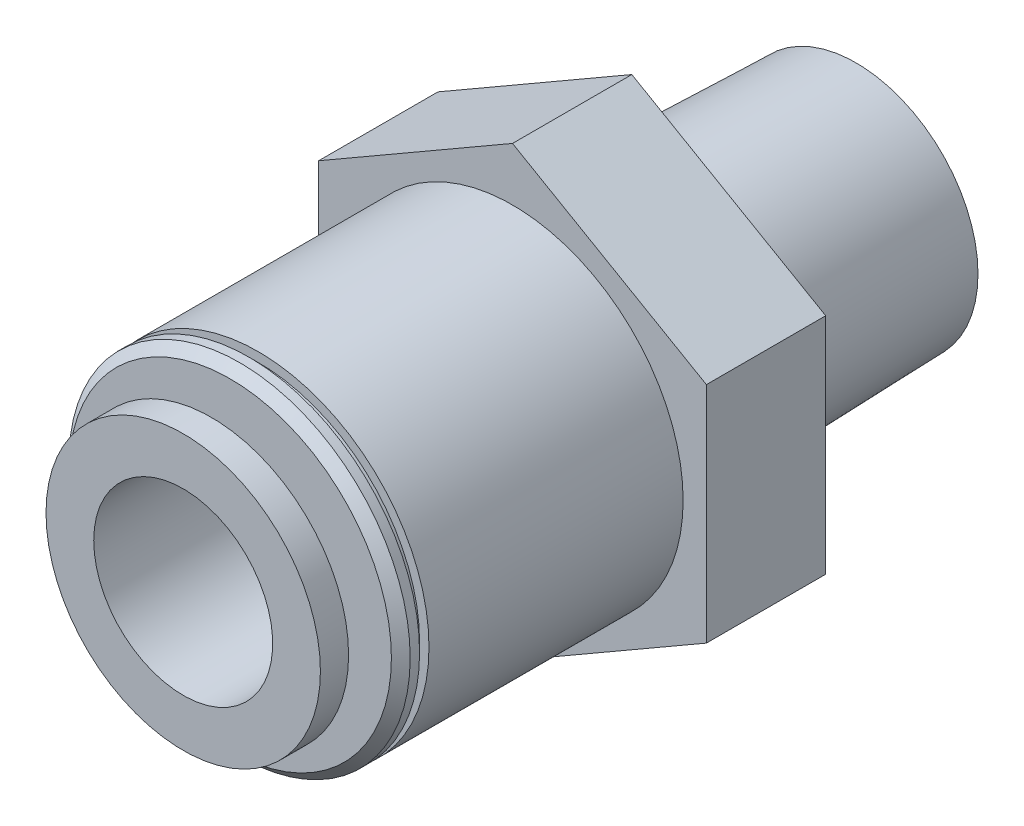
SolidWorks part; units mm, degrees
material "PP Copolymer"
ref_plane "Front Plane" through (0, 0, 0) normal (0, 0, 1) x (1, 0, 0)
ref_plane "Top Plane" through (0, 0, 0) normal (0, 1, 0) x (1, 0, 0)
ref_plane "Right Plane" through (0, 0, 0) normal (1, 0, 0) x (0, 0, -1)
sketch "Sketch1" plane through (0, 0, 0) normal (1, 0, 0) x (0, 0, -1)
  line L0 (-23.876, 0) -> (11.938, 0) construction
  line L1 (-23.876, 4.7625) -> (-23.876, -4.7625) construction
  line L2 (0, 6.858) -> (0, -6.858) construction
  line L3 (-6.35, 10.3187) -> (-6.35, -10.3187) construction
  line L4 (-6.35, 11.176) -> (-6.35, -11.176) construction
  line L5 (11.938, 3.81) -> (11.938, -3.81) construction
  line L6 (-23.876, 10.033) -> (-23.876, -10.033) construction
  line L7 (11.938, 4.6228) -> (11.938, -4.6228) construction
  point P8 (0, 0)
  point P11 (-6.35, 0)
  point P12 (-1.905, 0)
sketch "Sketch2" plane through (0, 0, 0) normal (1, 0, 0) x (0, 0, -1)
  line L0 (-23.876, 0) -> (-6.35, 0)
  line L1 (-6.35, 0) -> (-6.35, 9.0805)
  line L2 (-23.876, 0) -> (11.938, 0) construction
  line L3 (-6.35, 9.0805) -> (-19.876, 9.0805)
  line L4 (-21.376, 8.5805) -> (-20.876, 9.0805)
  line L5 (-21.376, 8.5805) -> (-21.376, 9.0805) construction
  line L6 (-21.376, 9.0805) -> (-20.876, 9.0805) construction
  line L7 (-21.376, 8.5805) -> (-21.376, 5.3975)
  line L8 (-21.376, 5.3975) -> (-22.376, 5.3975)
  line L9 (-22.376, 5.3975) -> (-22.376, 7.3025)
  line L10 (-22.376, 7.3025) -> (-23.876, 7.3025)
  line L11 (-23.876, 7.3025) -> (-23.876, 0)
  line L12 (-20.376, 9.0805) -> (-20.376, 8.5805)
  line L13 (-20.376, 8.5805) -> (-19.876, 8.5805)
  line L14 (-19.876, 8.5805) -> (-19.876, 9.0805)
  line L15 (-20.376, 9.0805) -> (-20.876, 9.0805)
  dimension "D6" = 0.5
revolve "Revolve1" add sketch "Sketch2" angle 360 about L0
sketch "Sketch3" plane through (0, 0, 6.35) normal (0, 0, -1) x (-1, 0, 0)
  line L0 (0, 10.3187) -> (0, -10.3187) construction
  line L1 (0, 11.9151) -> (-10.3187, 5.9575)
  line L2 (-10.3187, 5.9575) -> (-10.3187, -5.9575)
  line L3 (-10.3187, -5.9575) -> (0, -11.9151)
  line L4 (0, -11.9151) -> (10.3187, -5.9575)
  line L5 (10.3187, -5.9575) -> (10.3188, 5.9575)
  line L6 (10.3188, 5.9575) -> (0, 11.9151)
  circle A0 centre (0, 0) radius 10.3187 construction
extrude "Boss-Extrude1" add sketch "Sketch3" along normal up to vertex (6.35 mm away) up to point (0, 0, 0)
sketch "Sketch5" plane through (0, 0, 0) normal (0, 0, -1) x (-1, 0, 0)
  circle A0 centre (0, 0) radius 6.858
extrude "Boss-Extrude2" add sketch "Sketch5" along normal up to vertex (11.938 mm away) draft 1.783 separate body up to point (0, 0, -11.938)
combine bodies "Combine1" operation type add bodies to combine 103 105
sketch "Sketch9" plane through (0, 0, 0) normal (1, 0, 0) x (0, 0, -1)
  line L0 (-23.876, 4.7625) -> (-1.905, 4.7625)
  line L1 (-1.905, 4.7625) -> (-1.905, 3.81)
  line L2 (-1.905, 3.81) -> (-0.9568, 3.81)
  line L3 (11.938, 4.6228) -> (11.938, 0)
  line L4 (11.938, 3.81) -> (11.938, -3.81) construction
  line L5 (11.938, 0) -> (-23.876, 0)
  line L6 (-23.876, 0) -> (-23.876, 4.7625)
  line L7 (-1.905, 0) -> (-1.905, 3.81) construction
  line L8 (11.938, 4.6228) -> (-0.4684, 4.6228)
  line L9 (-0.4684, 4.6228) -> (-0.9568, 3.81)
  line L10 (-0.9568, 3.81) -> (11.938, 3.81) construction
  dimension "D1" = 59
revolve "Cut-Revolve2" cut sketch "Sketch9" angle 360 about L5
equation "\"D1@Sketch2\" = \"OD@Sketch1\" - 0.075"
equation "\"D2@Sketch2\" = \"Tube OD@Sketch1\" + 0.20"
equation "\"D3@Sketch2\" = \"Tube OD@Sketch1\" + 0.05"
